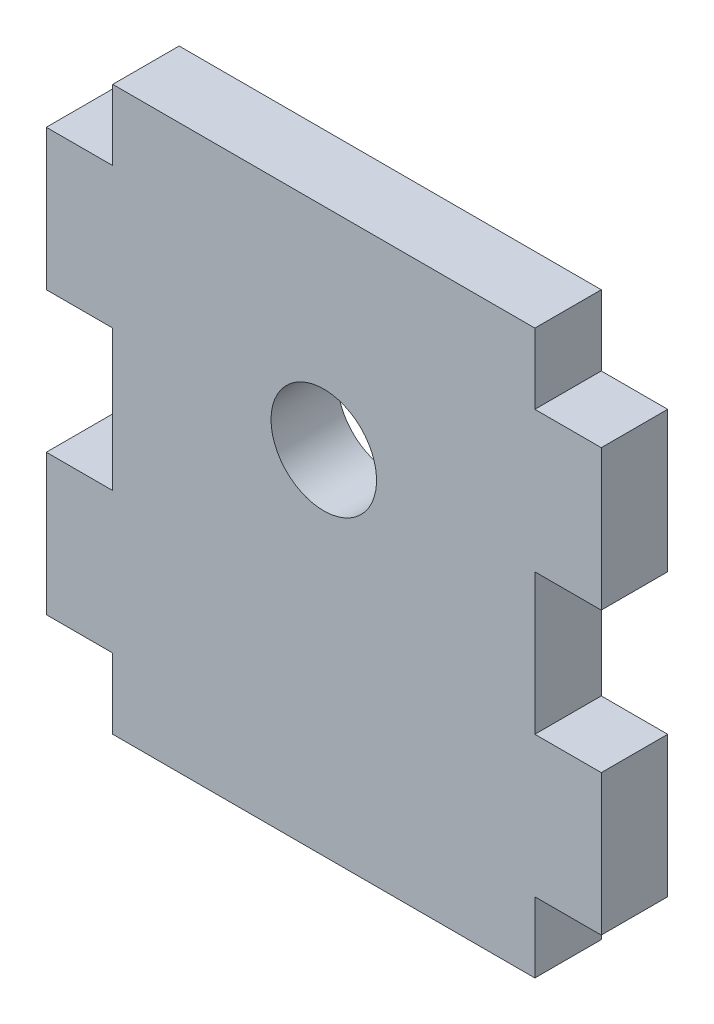
SolidWorks part; units mm, degrees
ref_plane "Front Plane" through (0, 0, 0) normal (0, 0, 1) x (1, 0, 0)
ref_plane "Top Plane" through (0, 0, 0) normal (0, 1, 0) x (1, 0, 0)
ref_plane "Right Plane" through (0, 0, 0) normal (1, 0, 0) x (0, 0, -1)
sketch "Sketch1" plane through (0, 0, 0) normal (0, 0, 1) x (1, 0, 0)
  line L0 (-19.05, 50.8) -> (-19.05, 0) construction
  line L1 (0, 0) -> (-38.1, 0)
  line L2 (0, 0) -> (0, 6.35)
  line L3 (0, 50.8) -> (-38.1, 50.8)
  line L4 (-38.1, 0) -> (-38.1, 6.35)
  line L5 (-38.1, 25.4) -> (0, 25.4) construction
  line L6 (-44.0944, 6.35) -> (-44.0944, 19.05)
  line L7 (-38.1, 44.45) -> (-44.0944, 44.45)
  line L8 (-38.1, 19.05) -> (-38.1, 31.75)
  line L9 (-38.1, 31.75) -> (-44.0944, 31.75)
  line L10 (-44.0944, 44.45) -> (-44.0944, 31.75)
  line L11 (-38.1, 19.05) -> (-44.0944, 19.05)
  line L12 (0, 19.05) -> (0, 31.75)
  line L13 (-38.1, 6.35) -> (-44.0944, 6.35)
  line L14 (0, 6.35) -> (5.9944, 6.35)
  line L15 (0, 44.45) -> (0, 50.8)
  line L16 (0, 19.05) -> (5.9944, 19.05)
  line L17 (5.9944, 44.45) -> (5.9944, 31.75)
  line L18 (0, 31.75) -> (5.9944, 31.75)
  line L20 (0, 44.45) -> (5.9944, 44.45)
  line L21 (5.9944, 6.35) -> (5.9944, 19.05)
  line L22 (-38.1, 44.45) -> (-38.1, 50.8)
  dimension "D1" = 38.1
  dimension "D2" = 50.8
  dimension "D3" = 12.7
  dimension "D4" = 5.9944
  dimension "D5" = 6.35
extrude "Boss-Extrude1" add sketch "Sketch1" along normal blind 5.9944
sketch "Sketch2" plane through (0, 0, 0) normal (0, 0, -1) x (-1, 0, 0)
  line L0 (19.05, 0) -> (19.05, 50.8) construction
  line L1 (38.1, 0) -> (0, 0) construction
  line L2 (0, 50.8) -> (38.1, 50.8) construction
  circle A0 centre (19.05, 31.75) radius 4.7625
  dimension "D1" = 19.05
  dimension "D2" = 9.525
extrude "Cut-Extrude1" cut sketch "Sketch2" against normal through all
